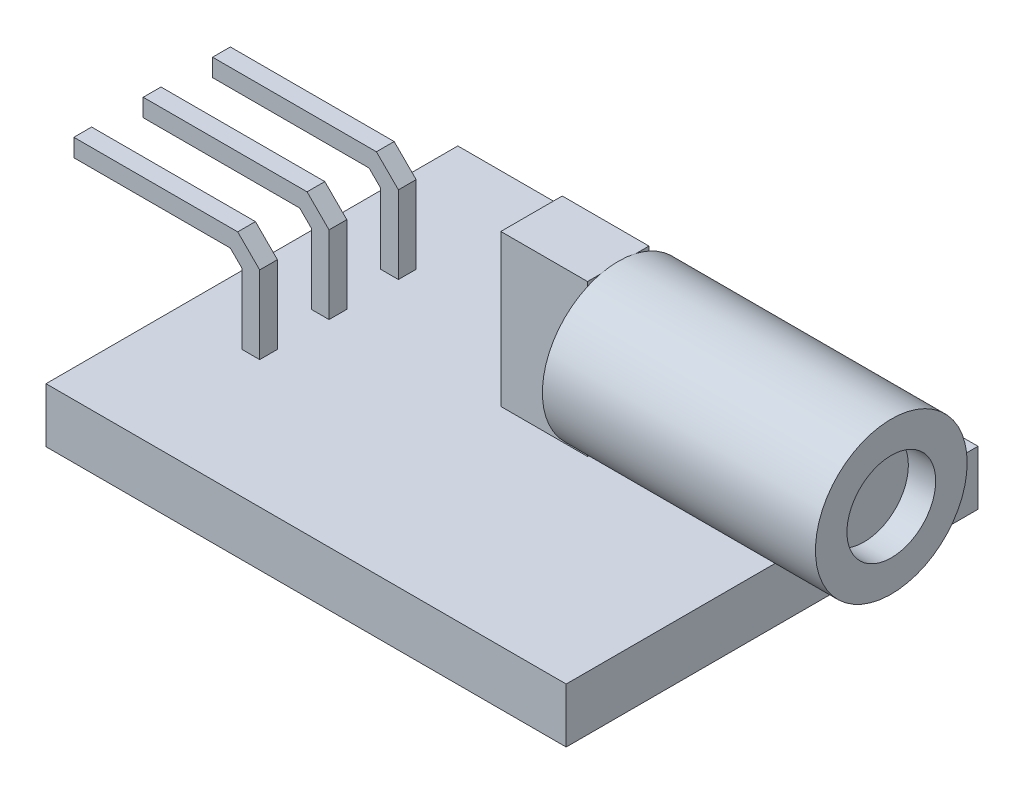
SolidWorks part; units mm, degrees
ref_plane "Front Plane" through (0, 0, 0) normal (0, 0, 1) x (1, 0, 0)
ref_plane "Top Plane" through (0, 0, 0) normal (0, 1, 0) x (1, 0, 0)
ref_plane "Right Plane" through (0, 0, 0) normal (1, 0, 0) x (0, 0, -1)
sketch "Sketch1" plane through (0, 0, 0) normal (0, 1, 0) x (1, 0, 0)
  line L1 (-9.525, -7.5406) -> (9.525, -7.5406)
  line L2 (-9.525, -7.5406) -> (-9.525, 7.5406)
  line L3 (-9.525, 7.5406) -> (9.525, 7.5406)
  line L4 (9.525, -7.5406) -> (9.525, 7.5406)
  line L5 (-9.525, -7.5406) -> (9.525, 7.5406) construction
  line L6 (-9.525, 7.5406) -> (9.525, -7.5406) construction
  point P0 (0, 0)
  dimension "D1" = 15.0813
  dimension "D2" = 19.05
extrude "Board" add sketch "Sketch1" along normal blind 2
ref_plane "Front of Barrel" through (12.7, 0, 0) normal (1, 0, 0) x (0, 0, -1)
sketch "Sketch2" plane through (12.7, 0, 0) normal (1, 0, 0) x (0, 0, -1)
  line L0 (-7.5406, 2) -> (7.5406, 2) construction
  line L1 (7.5406, 2) -> (7.5406, 0) construction
  circle A0 centre (1.1906, 4.85) radius 2.7781
  dimension "D1" = 5.5562
  dimension "D2" = 2.85
  dimension "D3" = 6.35
extrude "LaserBarrel" add sketch "Sketch2" against normal blind 10 separate body
sketch "Sketch4" plane through (2.7, 0, 0) normal (-1, 0, 0) x (0, 0, 1)
  line L0 (-7.5406, 2) -> (7.5406, 2) construction
  line L1 (-2.3156, 7.55) -> (-0.0656, 7.55)
  line L2 (-2.3156, 7.55) -> (-2.3156, 2)
  line L3 (-2.3156, 2) -> (-0.0656, 2)
  line L4 (-0.0656, 7.55) -> (-0.0656, 2)
  line L5 (-1.1906, 7.6281) -> (-1.1906, 2.0719) construction
  circle A0 centre (-1.1906, 4.85) radius 2.7781 construction
  point P11 (-1.1906, 7.55)
  dimension "D1" = 5.55
  dimension "D2" = 2.25
extrude "Barrel Butt Mount" add sketch "Sketch4" along normal blind 3.175
ref_axis "Axis1" through (2.7, 4.85, -1.1906) along (1, 0, 0)
ref_plane "Centerline of Barrel" through (0, 0, -1.1906) normal (0, 0, 1) x (1, 0, 0)
sketch "Centerline of Board" plane through (0, 2, 0) normal (0, 1, 0) x (1, 0, 0)
  line L0 (-9.525, 7.5406) -> (-9.525, -7.5406) construction
  point P0 (-9.525, 0)
sketch "Sketch5" plane through (0, 0, 0) normal (0, 0, 1) x (1, 0, 0)
  line L0 (-7.025, 2) -> (-6.375, 2)
  line L1 (-9.525, 2) -> (-9.525, 0) construction
  line L2 (-9.525, 2) -> (9.525, 2) construction
  line L3 (-6.375, 2) -> (-6.375, 4.845)
  line L4 (-6.375, 4.845) -> (-7.18, 5.65)
  line L5 (-7.18, 5.65) -> (-13.18, 5.65)
  line L6 (-13.18, 5.65) -> (-13.18, 5)
  line L7 (-13.18, 5) -> (-7.4493, 5)
  line L8 (-7.4493, 5) -> (-7.025, 4.5757)
  line L9 (-7.025, 4.5757) -> (-7.025, 2)
  dimension "D1" = 0.65
  dimension "D2" = 6
  dimension "D3" = 0.65
  dimension "D4" = 0.65
  dimension "D5" = 3
  dimension "D6" = 0.6
  dimension "D7" = 225
  dimension "D8" = 2.5
extrude "Boss-Extrude1" add sketch "Sketch5" along normal mid plane 0.65
pattern_linear "LPattern1" count 2 spacing 2.54 along (0, 0, -1) count 2 spacing 2.54 along (0, 0, 1) of "Boss-Extrude1"
sketch "Sketch6" plane through (12.7, 0, 0) normal (1, 0, 0) x (0, 0, -1)
  circle A0 centre (1.1906, 4.85) radius 1.625
  dimension "D1" = 3.25
extrude "Cut-Extrude1" cut sketch "Sketch6" against normal blind 1
equation "\"D3@Sketch5\"=\"D1@Sketch5\""
equation "\"D4@Sketch5\"=\"D1@Sketch5\""
